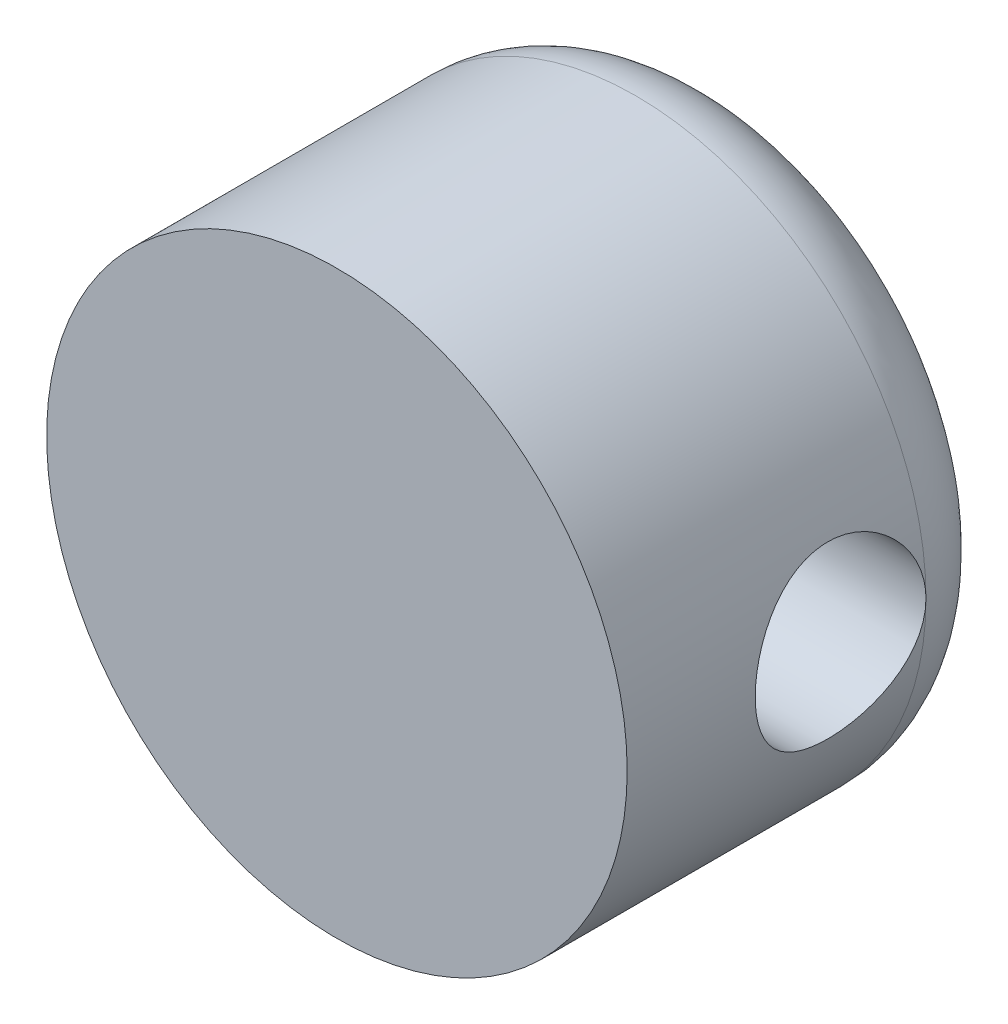
SolidWorks part; units mm, degrees
ref_plane "Front Plane" through (0, 0, 0) normal (0, 0, 1) x (1, 0, 0)
ref_plane "Top Plane" through (0, 0, 0) normal (0, 1, 0) x (1, 0, 0)
ref_plane "Right Plane" through (0, 0, 0) normal (1, 0, 0) x (0, 0, -1)
sketch "Sketch1" plane through (0, 0, 0) normal (0, 0, 1) x (1, 0, 0)
  circle A0 centre (0, 0) radius 3.4
extrude "Boss-Extrude1" add sketch "Sketch1" along normal blind 4.5
sketch "Sketch2" plane through (4, 0, 0) normal (1, 0, 0) x (0, 0, -1)
  circle A0 centre (-2, 0) radius 1
extrude "Cut-Extrude1" cut sketch "Sketch2" against normal blind 10
fillet "Fillet1" radius 1 1 edges at (3.4, 0, 0)
